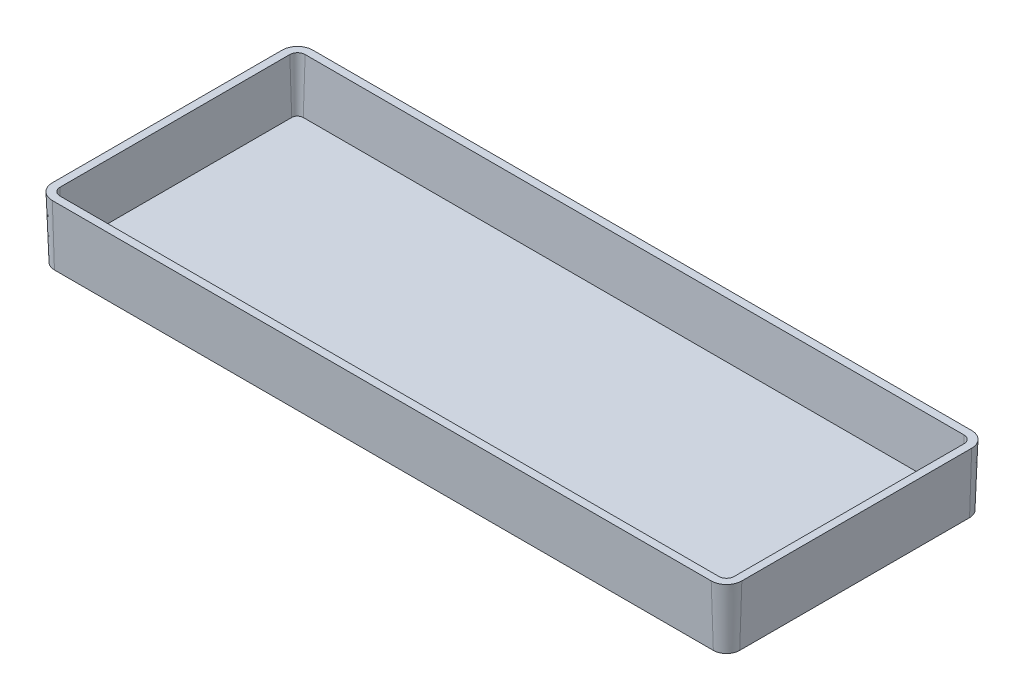
SolidWorks part; units mm, degrees
ref_plane "Front Plane" through (0, 0, 0) normal (0, 0, 1) x (1, 0, 0)
ref_plane "Top Plane" through (0, 0, 0) normal (0, 1, 0) x (1, 0, 0)
ref_plane "Right Plane" through (0, 0, 0) normal (1, 0, 0) x (0, 0, -1)
sketch "Sketch1" plane through (0, 0, 0) normal (0, 1, 0) x (1, 0, 0)
  line L1 (-21.5, -8.5) -> (21.5, -8.5)
  line L2 (-22.5, -7.5) -> (-22.5, 7.5)
  line L3 (-21.5, 8.5) -> (21.5, 8.5)
  line L4 (22.5, -7.5) -> (22.5, 7.5)
  line L5 (-22.5, -8.5) -> (22.5, 8.5) construction
  line L6 (-22.5, 8.5) -> (22.5, -8.5) construction
  arc A0 (-22.5, 7.5) -> (-21.5, 8.5) centre (-21.5, 7.5) cw
  arc A1 (22.5, 7.5) -> (21.5, 8.5) centre (21.5, 7.5) ccw
  arc A2 (22.5, -7.5) -> (21.5, -8.5) centre (21.5, -7.5) cw
  arc A3 (-21.5, -8.5) -> (-22.5, -7.5) centre (-21.5, -7.5) cw
  point P0 (0, 0)
  dimension "D3" = 1
  dimension "D1" = 45
  dimension "D2" = 17
extrude "Boss-Extrude1" add sketch "Sketch1" against normal blind 4 draft 2
shell "Shell1" thickness 0.5 removed face at (0, 0, 0)
